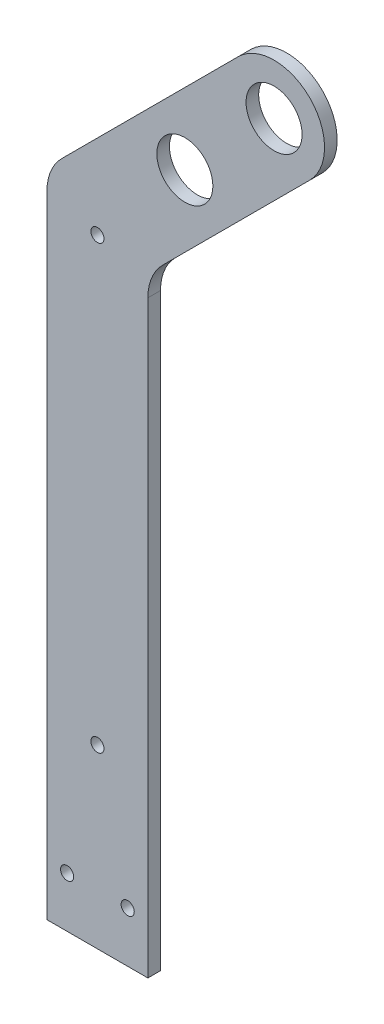
SolidWorks part; units mm, degrees
material "6061 合金"
ref_plane "前视基准面" through (0, 0, 0) normal (0, 0, 1) x (1, 0, 0)
ref_plane "上视基准面" through (0, 0, 0) normal (0, 1, 0) x (1, 0, 0)
ref_plane "右视基准面" through (0, 0, 0) normal (1, 0, 0) x (0, 0, -1)
other "Configuration Table"
sketch "草图1" plane through (0, 0, 0) normal (0, 0, 1) x (1, 0, 0)
  circle A0 centre (0, 0) radius 20
  circle A1 centre (0, 0) radius 11.1
  dimension "D1" = 40
  dimension "D2" = 22.2
extrude "凸台-拉伸1" add sketch "草图1" along normal blind 60 contours A1 | A0 region at (0, 0, 0)
ref_plane "基准面1" through (0, 0, 30) normal (0, 0, 1) x (1, 0, 0)
sketch "草图2" plane through (0, 0, 30) normal (0, 0, 1) x (1, 0, 0)
  line L0 (0, 0) -> (-70, -70) construction
  line L1 (-70, -70) -> (-70, -320) construction
  line L2 (0, -57.3148) -> (0, 49.9409) construction
  line L3 (-56.8582, 0) -> (46.4003, 0) construction
  line L4 (-14.1421, 14.1421) -> (-90, -61.7157)
  line L5 (14.1421, -14.1421) -> (-50, -78.2843)
  line L6 (-90, -61.7157) -> (-90, -320)
  line L7 (-50, -78.2843) -> (-50, -320)
  line L8 (-90, -320) -> (-50, -320)
  circle A2 centre (0, 0) radius 20 construction
  arc A3 (-14.1421, 14.1421) -> (14.1421, -14.1421) centre (0, 0) ccw
  dimension "D1" = 45
  dimension "D2" = 250
  dimension "D3" = 70
  dimension "D4" = 40
  dimension "D5" = 40
extrude "凸台-拉伸2" add sketch "草图2" along normal mid plane 60 contours L7 L8 L6 L4 A3 L5
sketch "草图4" plane through (0, 0, 60) normal (0, 0, 1) x (1, 0, 0)
  line L0 (-90, -61.7157) -> (-90, -320) construction
  line L1 (-90, -290) -> (-50, -290)
  line L2 (-90, -290) -> (-90, -350)
  line L4 (-50, -290) -> (-50, -350)
  line L5 (-50, -78.2843) -> (-50, -320) construction
  line L6 (-90, -320) -> (-50, -320) construction
  arc A0 (-90, -350) -> (-50, -350) centre (-70, -350) ccw
  circle A1 centre (-70, -350) radius 11
  dimension "D3" = 22
  dimension "D1" = 30
  dimension "D2" = 30
extrude "凸台-拉伸3" add sketch "草图4" along normal blind 5
mirror "镜向1" about plane through (0, 0, 30) normal (0, 0, 1) of "凸台-拉伸3"
sketch "草图5" plane through (0, 0, 0) normal (0, 1, 0) x (1, 0, 0)
  line L0 (0, 0) -> (0, -78.0582) construction
ref_plane "基准面2" through (-70, 0, 0) normal (-1, 0, 0) x (0, 0, 1)
sketch "草图7" plane through (-70, 0, 0) normal (-1, 0, 0) x (0, 0, 1)
  line L0 (-34.1239, -350) -> (109.535, -350) construction
sketch "草图8" plane through (0, 0, 60) normal (0, 0, 1) x (1, 0, 0)
  line L0 (0, 0) -> (-70, -70) construction
  circle A0 centre (-35.3553, -35.3553) radius 11.1
  dimension "D1" = 22.2
  dimension "D2" = 50
extrude "切除-拉伸1" cut sketch "草图8" against normal blind 100
fillet "圆角4" radius 20 2 edges at (-90, -61.7157, 30) (-50, -78.2843, 30)
fillet "圆角1" [suppressed] radius 50
fillet "圆角2" [suppressed] radius 3
sketch "草图9" plane through (0, 0, 65) normal (0, 0, 1) x (1, 0, 0)
  circle A0 centre (-70, -350) radius 13
  dimension "D1" = 26
extrude "切除-拉伸2" [suppressed] cut sketch "草图9" against normal blind 0.75
sketch "草图10" plane through (0, 0, -5) normal (0, 0, -1) x (-1, 0, 0)
  circle A0 centre (70, -350) radius 13
  dimension "D1" = 26
extrude "切除-拉伸3" [suppressed] cut sketch "草图10" against normal blind 0.75 contours A0
sketch "草图11" plane through (-90, 0, 0) normal (-1, 0, 0) x (0, 0, 1)
  circle A0 centre (48.5, -118.9949) radius 2.75
  circle A1 centre (48.5, -183.9949) radius 2.75
  circle A2 centre (48.5, -248.9949) radius 2.75
  circle A3 centre (11.5, -248.9949) radius 2.75
  circle A4 centre (11.5, -183.9949) radius 2.75
  circle A5 centre (11.5, -118.9949) radius 2.75
  dimension "D1" = 5.5
extrude "切除-拉伸4" [suppressed] cut sketch "草图11" against normal through all contours A1 | A2 | A0 | A3 | A4 | A5
sketch "草图12" [suppressed] plane through (-90, 0, 0) normal (-1, 0, 0) x (0, 0, 1)
  line L0 (30, -62.0134) -> (30, -339.6946) construction
  line L1 (10, -128.9949) -> (50, -128.9949)
  line L2 (10, -128.9949) -> (10, -173.9949)
  line L3 (10, -173.9949) -> (50, -173.9949)
  line L4 (50, -128.9949) -> (50, -173.9949)
  line L5 (10, -193.9949) -> (50, -193.9949)
  line L6 (10, -193.9949) -> (10, -238.9949)
  line L7 (10, -238.9949) -> (50, -238.9949)
  line L8 (50, -193.9949) -> (50, -238.9949)
  line L9 (10, -258.9949) -> (50, -258.9949)
  line L10 (10, -258.9949) -> (10, -290)
  line L11 (10, -290) -> (50, -290)
  line L12 (50, -258.9949) -> (50, -290)
  line L13 (19.5, -173.9949) -> (40.5, -173.9949)
  line L14 (19.5, -173.9949) -> (19.5, -193.9949)
  line L15 (19.5, -193.9949) -> (40.5, -193.9949)
  line L16 (40.5, -173.9949) -> (40.5, -193.9949)
  line L17 (19.5, -238.9949) -> (40.5, -238.9949)
  line L18 (19.5, -238.9949) -> (19.5, -258.9949)
  line L19 (19.5, -258.9949) -> (40.5, -258.9949)
  line L20 (40.5, -238.9949) -> (40.5, -258.9949)
  line L21 (60, -82.4264) -> (60, -290) construction
  line L22 (0, -290) -> (0, -82.4264) construction
  line L23 (57, -320) -> (3, -320) construction
  circle A0 centre (48.5, -118.9949) radius 2.75 construction
  circle A1 centre (48.5, -183.9949) radius 2.75 construction
  circle A2 centre (48.5, -248.9949) radius 2.75 construction
  dimension "D1" = 10
  dimension "D2" = 10
  dimension "D3" = 10
  dimension "D4" = 8
  dimension "D5" = 10
  dimension "D6" = 10
  dimension "D7" = 10
  dimension "D8" = 30
extrude "减重" [suppressed] cut sketch "草图12" against normal through all contours L0 L1 L2 L3 | L15 L0 L17 L7 L8 L5 | L0 L5 L6 L7 | L19 L0 L11 L12 L9 | L0 L9 L10 L11 | L1 L0 L13 L3 L4
fillet "圆角3" [suppressed] radius 3
sketch "草图13" plane through (0, 0, 60) normal (0, 0, 1) x (1, 0, 0)
  circle A0 centre (0, 0) radius 13
  circle A1 centre (-35.3553, -35.3553) radius 13
  dimension "D1" = 26
  dimension "D2" = 26
extrude "切除-拉伸6" [suppressed] cut sketch "草图13" against normal blind 1.75
sketch "草图14" plane through (0, 0, 0) normal (0, 0, -1) x (-1, 0, 0)
  circle A0 centre (0, 0) radius 13
  circle A1 centre (35.3553, -35.3553) radius 13
  dimension "D1" = 26
  dimension "D2" = 26
extrude "切除-拉伸7" [suppressed] cut sketch "草图14" against normal blind 1.75
sketch "草图15" [suppressed] plane through (0, 0, 0) normal (0, 0, -1) x (-1, 0, 0)
  line L0 (0, 0) -> (70, -350) construction
  line L1 (56.2719, -67.2005) -> (60.1942, -86.8121) construction
  line L2 (70, -350) -> (204.3541, -323.1292) construction
  circle A0 centre (56.2719, -67.2005) radius 2.75
  circle A1 centre (75.2172, -73.6095) radius 2.75
  circle A2 centre (60.1942, -86.8121) radius 2.75
  dimension "D1" = 5.5
  dimension "D2" = 20
  dimension "D3" = 20
  dimension "D4" = 20
  dimension "D5" = 42
  dimension "D6" = 270
extrude "切除-拉伸8" [suppressed] cut sketch "草图15" against normal through all contours A2 | A0 | A1
ref_plane "小腿主干连杆面" through (0, 0, 0) normal (0.9806, -0.1961, 0) x (0, 0, -1)
ref_plane "小腿主干对称面" through (0, 0, 30) normal (0, 0, -1) x (-1, 0, 0)
sketch "草图16" plane through (0, 0, 60) normal (0, 0, 1) x (1, 0, 0)
  line L0 (0, 0) -> (-70, -350)
  line L1 (-35.3553, -35.3553) -> (0, 0)
sketch "草图17" plane through (0, 0, 60) normal (0, 0, 1) x (1, 0, 0)
  line L0 (0, 0) -> (-70, -350) construction
  line L1 (118.6974, 32.5948) -> (32.9122, -396.3312) construction
  line L2 (92.7764, -97.0102) -> (20.2919, -82.5133)
  line L3 (73.1648, -195.0683) -> (0.6803, -180.5713)
  circle A0 centre (20.2919, -82.5133) radius 46
  circle A1 centre (0.6803, -180.5713) radius 46
  dimension "D3" = 92
  dimension "D4" = 92
  dimension "D1" = 110
  dimension "D2" = 73.92
  dimension "D5" = 180
  dimension "D6" = 280
sketch "草图18" plane through (0, 0, 60) normal (0, 0, 1) x (1, 0, 0)
  line L1 (14.1421, -14.1421) -> (-44.1421, -72.4264) construction
  line L3 (14.1421, -14.1421) -> (-44.1421, -72.4264)
  line L4 (15.4873, -12.6548) -> (52.8188, -49.9864)
  line L5 (-50, -128.5133) -> (20.2919, -128.5133)
  line L10 (-90, -290) -> (-50, -290)
  line L11 (-50, -290) -> (-50, -86.5685)
  line L12 (-44.1421, -72.4264) -> (14.1421, -14.1421)
  line L13 (-14.1421, 14.1421) -> (-84.1421, -55.8579)
  line L14 (-90, -70) -> (-90, -290)
  line L16 (-50, -128.5133) -> (-50, -86.5685)
  line L17 (-44.1421, -72.4264) -> (14.1421, -14.1421)
  circle A0 centre (20.2919, -82.5133) radius 46 construction
  arc A1 (14.1421, -14.1421) -> (-14.1421, 14.1421) centre (0, 0) ccw construction
  arc A2 (14.1421, -14.1421) -> (-14.1421, 14.1421) centre (0, 0) ccw
  arc A3 (14.1421, -14.1421) -> (15.4873, -12.6548) centre (0, 0) ccw
  arc A4 (20.2919, -128.5133) -> (52.8188, -49.9864) centre (20.2919, -82.5133) ccw
  circle A5 centre (20.2919, -82.5133) radius 35
  arc A9 (-84.1421, -55.8579) -> (-90, -70) centre (-70, -70) ccw
  arc A10 (-84.1421, -55.8579) -> (-90, -70) centre (-70, -70) ccw
  arc A11 (-44.1421, -72.4264) -> (-50, -86.5685) centre (-30, -86.5685) ccw
  arc A12 (-44.1421, -72.4264) -> (-50, -86.5685) centre (-30, -86.5685) ccw
  line M14 (-50, -290) -> (-50, -86.5685)
  line M15 (-44.1421, -72.4264) -> (14.1421, -14.1421)
  arc M16 (14.1421, -14.1421) -> (-14.1421, 14.1421) centre (0, 0) ccw
  arc M22 (-50, -86.5685) -> (-44.1421, -72.4264) centre (-30, -86.5685) cw
  dimension "D2" = 70
  dimension "D1" = 0
extrude "凸台-拉伸4" add sketch "草图18" against normal blind 5 from offset 25 contours L5 A4 L4 A5 M16 M15 M22 M14 region at (16.0508, -14.5165, 60) offset against normal yes
sketch "草图19" plane through (0, 0, 0) normal (0, 0, -1) x (-1, 0, 0)
  line L0 (50, -86.5685) -> (50, -290) construction
  line L1 (50, -134.5713) -> (50, -226.5713)
  line L2 (-0.6803, -134.5713) -> (50, -134.5713)
  line L3 (-0.6803, -226.5713) -> (50, -226.5713)
  circle A0 centre (-0.6803, -180.5713) radius 46 construction
  arc A1 (-0.6803, -134.5713) -> (-0.6803, -226.5713) centre (-0.6803, -180.5713) ccw
  circle A2 centre (-0.6803, -180.5713) radius 35
  dimension "D1" = 70
extrude "凸台-拉伸5" add sketch "草图19" against normal blind 5 from offset 25 offset against normal yes
fillet "圆角5" radius 10 2 edges at (-50, -226.5713, 27.5) (-50, -128.5133, 32.5)
sketch "草图21" plane through (0, 0, 65) normal (0, 0, 1) x (1, 0, 0)
  line L0 (-70, -350) -> (-70, -6.9331) construction
  circle A0 centre (-70, -75) radius 2.6
  circle A1 centre (-70, -250) radius 2.6
  circle A2 centre (-58, -300) radius 2.6
  circle A3 centre (-82, -300) radius 2.6
  dimension "D1" = 5.2
  dimension "D2" = 12
  dimension "D3" = 50
  dimension "D4" = 100
  dimension "D5" = 175
extrude "切除-拉伸9" cut sketch "草图21" against normal through all both and the other way through all
sketch "草图22" plane through (-90, 0, 0) normal (-1, 0, 0) x (0, 0, 1)
  line L0 (-5, -350) -> (-5, -370) construction
  line L5 (-5, -387.3952) -> (15, -387.3952)
  line L6 (-5, -387.3952) -> (-5, 64.9179)
  line L7 (-5, 64.9179) -> (15, 64.9179)
  line L8 (15, -387.3952) -> (15, 64.9179)
  line L10 (65, -370) -> (20, -370)
  line L11 (65, -370) -> (65, 61.088)
  line L12 (65, 61.088) -> (20, 61.088)
  line L13 (20, -370) -> (20, 61.088)
  dimension "D1" = 45
  dimension "D2" = 5
extrude "切除-拉伸10" cut sketch "草图22" against normal through all both contours L8 L7 L6 L5 | L13 L12 L11 L10
